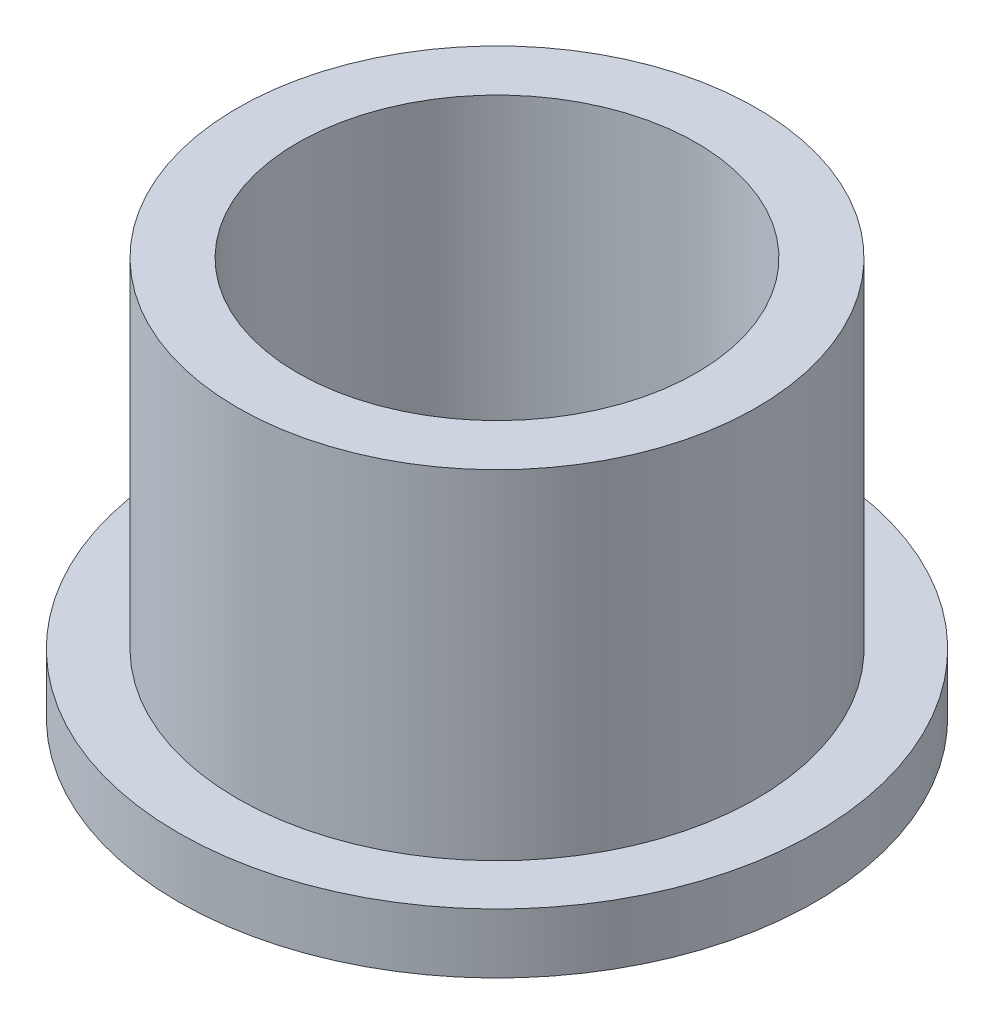
SolidWorks part; units mm, degrees
material "Brass"
ref_plane "Front" through (0, 0, 0) normal (0, 0, 1) x (1, 0, 0)
ref_plane "Top" through (0, 0, 0) normal (0, 1, 0) x (1, 0, 0)
ref_plane "Right" through (0, 0, 0) normal (1, 0, 0) x (0, 0, -1)
sketch "Sketch1" plane through (0, 0, 0) normal (0, 1, 0) x (1, 0, 0)
  circle A0 centre (0, 0) radius 5.005
  circle A1 centre (0, 0) radius 6.515
  circle A2 centre (0, 0) radius 8
  dimension "ID" = 10.01
  dimension "OD" = 13.03
  dimension "FlangeOD" = 16
sketch "Sketch2" plane through (0, 0, 0) normal (0, 1, 0) x (1, 0, 0)
  circle A0 centre (0, 0) radius 5.005 construction
  circle A1 centre (0, 0) radius 6.515 construction
  circle A2 centre (0, 0) radius 5.005
  circle A3 centre (0, 0) radius 6.515
extrude "Boss-Extrude1" add sketch "Sketch2" along normal blind 10
sketch "Sketch3" plane through (0, 0, 0) normal (0, 1, 0) x (1, 0, 0)
  circle A0 centre (0, 0) radius 8 construction
  circle A1 centre (0, 0) radius 6.515 construction
  circle A2 centre (0, 0) radius 8
  circle A3 centre (0, 0) radius 6.515
extrude "Boss-Extrude2" add sketch "Sketch3" along normal blind 1.5
ref_axis "Center Axis 1" through (0, 10, 0) along (0, -1, 0)
